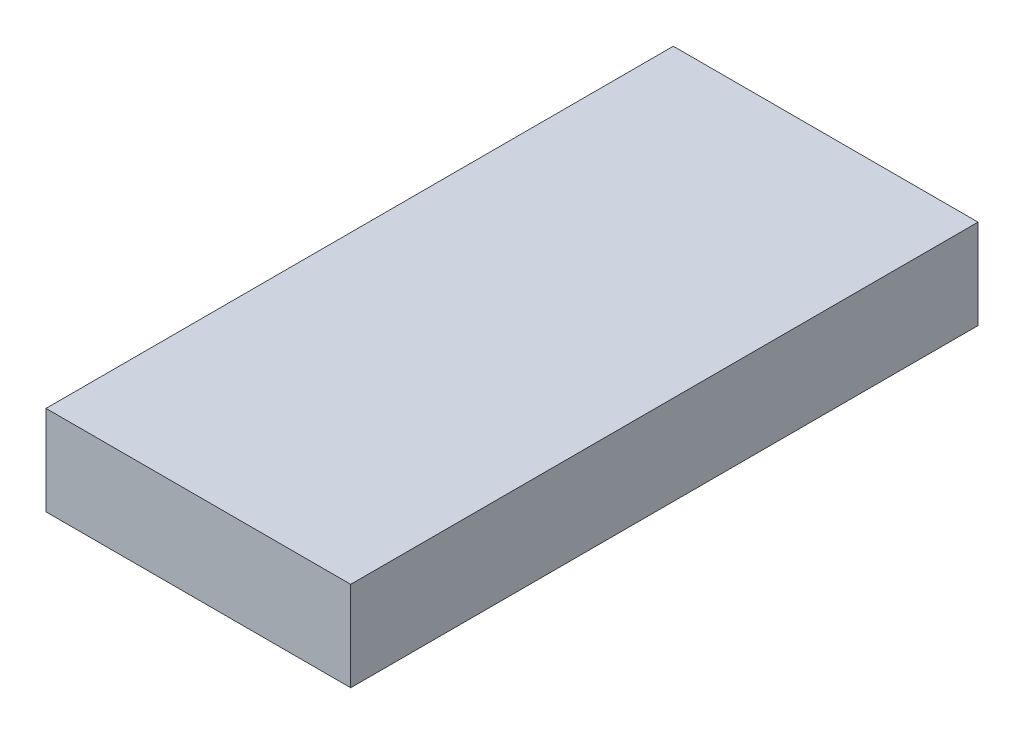
SolidWorks part; units mm, degrees
ref_plane "Front Plane" through (0, 0, 0) normal (0, 0, 1) x (1, 0, 0)
ref_plane "Top Plane" through (0, 0, 0) normal (0, 1, 0) x (1, 0, 0)
ref_plane "Right Plane" through (0, 0, 0) normal (1, 0, 0) x (0, 0, -1)
sketch "Sketch2" plane through (0, 0, 0) normal (0, 1, 0) x (1, 0, 0)
  line L0 (-279.9509, 0) -> (13717.5932, 0) construction
  line L1 (0, -279.9509) -> (0, 13717.5932) construction
  line L3 (-8.5, 17.5) -> (8.5, 17.5)
  line L4 (-8.5, 17.5) -> (-8.5, -17.5)
  line L5 (-8.5, -17.5) -> (8.5, -17.5)
  line L6 (8.5, 17.5) -> (8.5, -17.5)
  line L7 (-8.5, 17.5) -> (8.5, -17.5) construction
  line L8 (-8.5, -17.5) -> (8.5, 17.5) construction
  point P4 (0, 0)
  dimension "D1" = 17
  dimension "D2" = 35
extrude "Boss-Extrude1" add sketch "Sketch2" along normal blind 5
equation "\"Frame_Size\" = 220"
equation "\"Frame_Thickness\" = 6"
equation "\"Arm_Width\" = 30"
equation "\"Motor_Mount_Hole_Diameter\" = 8"
equation "\"Motor_Shaft_Diameter\" = 3"
equation "\"Screw_Nut_Diameter\" = 6.5"
equation "\"Screw_Diameter\" = 3"
equation "\"Screw_Shaft_Length\" = 10"
equation "\"Screw_Hole_Separation_C2C\" = 20"
equation "\"Solder_Board_Small_Screw_Hole_Separation\" = 37"
equation "\"Solder_Board_Small_Screw_Hole_Diameter\" = 3.3"
equation "\"Solder_Board_Small_Length\" = 45.72"
equation "\"Solder_Board_Small_Width\" = 33.02"
equation "\"Solder_Board_Small_Thickness\" = 1.6"
equation "\"ESC_Length\" = 35"
equation "\"ESC_Width\" = 17"
equation "\"ESC_Thickness\" = 5"
equation "\"D1@Sketch2\"=\"ESC_Width\""
equation "\"D2@Sketch2\"=\"ESC_Length\""
equation "\"D1@Boss-Extrude1\"=\"ESC_Thickness\""
